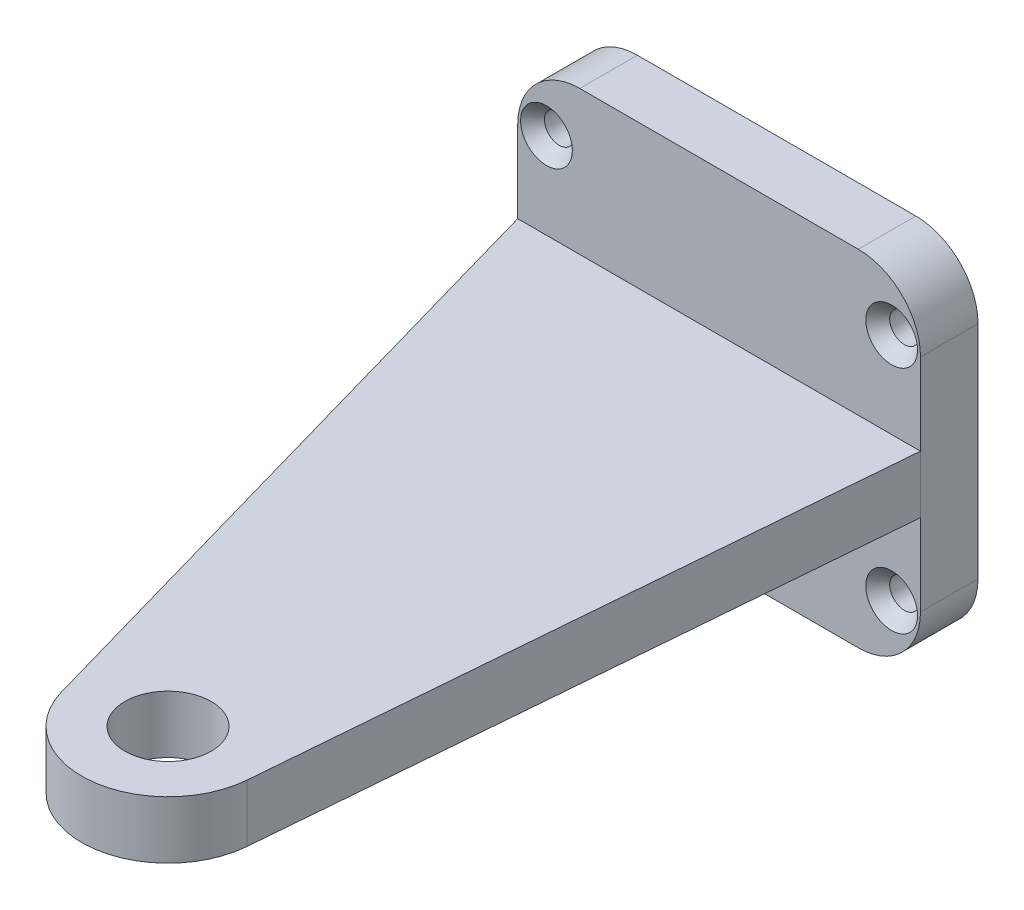
SolidWorks part; units mm, degrees
material "6061-T6 (SS)"
ref_plane "XY" through (0, 0, 0) normal (0, 0, 1) x (1, 0, 0)
ref_plane "XZ" through (0, 0, 0) normal (0, 1, 0) x (1, 0, 0)
ref_plane "YZ" through (0, 0, 0) normal (1, 0, 0) x (0, 0, -1)
ref_axis "X" through (-27.94, 0, 0) along (1, 0, 0)
ref_axis "Y" through (0, -20.955, 0) along (0, 1, 0)
ref_axis "Z" through (0, 0, 6.6675) along (0, 0, -1)
sketch "Sketch1" plane through (0, 0, 0) normal (0, 0, 1) x (1, 0, 0)
  line L1 (-22.225, -19.05) -> (22.225, -19.05)
  line L2 (-22.225, -19.05) -> (-22.225, 19.05)
  line L3 (-22.225, 19.05) -> (22.225, 19.05)
  line L4 (22.225, -19.05) -> (22.225, 19.05)
  line L5 (-22.225, -19.05) -> (22.225, 19.05) construction
  line L6 (-22.225, 19.05) -> (22.225, -19.05) construction
  point P0 (0, 0)
  dimension "D1" = 38.1
  dimension "D2" = 44.45
extrude "Boss-Extrude1" add sketch "Sketch1" along normal blind 6.35
hole_wizard "CSK for #4 Flat Head Machine Screw1" positions "Sketch2" profile "Sketch3" countersink size "#4" standard "ANSI Inch" end condition up to next
sketch "Sketch2" plane through (0, 0, 6.35) normal (0, 0, 1) x (1, 0, 0)
  line L1 (-19.05, 12.7) -> (19.05, 12.7)
  line L2 (-19.05, 12.7) -> (-19.05, -12.7)
  line L3 (-19.05, -12.7) -> (19.05, -12.7)
  line L4 (19.05, 12.7) -> (19.05, -12.7)
  line L5 (0, -12.7) -> (0, 12.7) construction
  point P0 (-19.05, 12.7)
  point P5 (19.05, -12.7)
  point P108 (-19.05, -12.7)
  point P109 (19.05, 12.7)
  dimension "D1" = 25.4
  dimension "D2" = 38.1
sketch "Sketch3" plane through (-19.05, 12.7, 6.35) normal (1, 0, 0) x (0, -1, 0)
  line L0 (0, 0) -> (0, 6.35)
  line L1 (0, 6.35) -> (1.6319, 6.35)
  line L2 (1.6319, 6.35) -> (1.6319, 1.4098)
  line L3 (1.6319, 1.4098) -> (2.8575, 0)
  line L5 (2.8575, 0) -> (0, 0)
  line L6 (-1.6319, 1.4098) -> (-2.8575, 0) construction
  line L11 (0, -6.35) -> (0, 107.95) construction
  dimension "Thru Hole Dia." = 3.2639
  dimension "Thru Hole Depth" = 6.35
  dimension "Near C'Sink Dia." = 5.715
  dimension "Near C'Sink Angle" = 82
sketch "Sketch4" plane through (0, 0, 0) normal (0, 1, 0) x (1, 0, 0)
  line L0 (0, 0) -> (7, -74.168) construction
  line L1 (-2.1605, -76.7778) -> (-22.225, -6.35)
  line L2 (-22.225, -6.35) -> (22.225, -6.35) construction
  line L3 (16.4919, -74.9611) -> (22.225, -6.35)
  line L4 (-22.225, -6.35) -> (22.225, -6.35)
  line L5 (22.225, 0) -> (-22.225, 0) construction
  circle A0 centre (7, -74.168) radius 8.382 construction
  circle A1 centre (7, -74.168) radius 4.7625
  arc A2 (-2.1605, -76.7778) -> (16.4919, -74.9611) centre (7, -74.168) ccw
  dimension "D1" = 16.764
  dimension "D3" = 9.525
  dimension "D4" = 19.05
  dimension "D2" = 74.168
  dimension "D5" = 7
extrude "Boss-Extrude2" add sketch "Sketch4" along normal mid plane 6.35
fillet "Fillet2" radius 6.858 4 edges at (-22.225, 19.05, 3.175) (-22.225, -19.05, 3.175) (22.225, -19.05, 3.175) (22.225, 19.05, 3.175)
